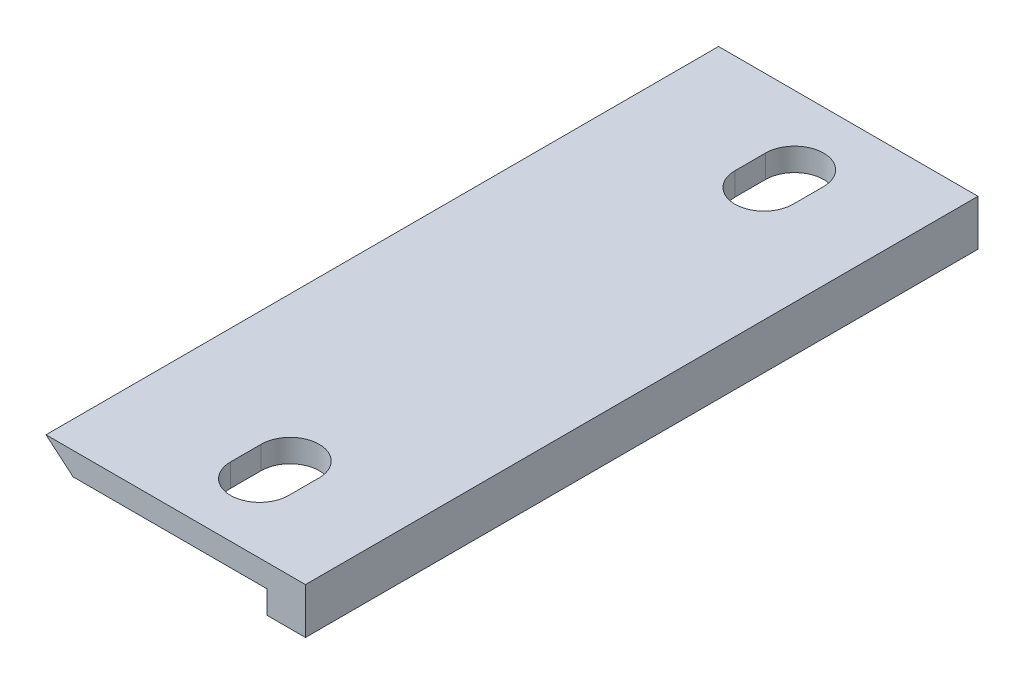
SolidWorks part; units mm, degrees
ref_plane "Спереди" through (0, 0, 0) normal (0, 0, 1) x (1, 0, 0)
ref_plane "Сверху" through (0, 0, 0) normal (0, 1, 0) x (1, 0, 0)
ref_plane "Справа" through (0, 0, 0) normal (1, 0, 0) x (0, 0, -1)
sketch "Эскиз1" plane through (0, 0, 0) normal (0, 0, 1) x (1, 0, 0)
  line L0 (169.7482, 0) -> (0, 0)
  line L1 (17.7482, -15) -> (144.7482, -15)
  line L2 (144.7482, -15) -> (144.7482, -30)
  line L3 (169.7482, -30) -> (144.7482, -30)
  line L9 (169.7482, -30) -> (169.7482, 0)
  line L10 (0, 0) -> (17.7482, -15)
extrude "Бобышка-Вытянуть1" add sketch "Эскиз1" against normal blind 440
sketch "Эскиз4" plane through (0, 0, 0) normal (0, 1, 0) x (1, 0, 0)
  line L0 (75.7482, 65) -> (75.7482, 45)
  line L1 (113.7482, 45) -> (113.7482, 65)
  line L2 (75.7482, 395) -> (75.7482, 375)
  line L3 (113.7482, 375) -> (113.7482, 395)
  arc A0 (75.7482, 45) -> (113.7482, 45) centre (94.7482, 45) ccw
  arc A1 (113.7482, 65) -> (75.7482, 65) centre (94.7482, 65) ccw
  arc A2 (75.7482, 375) -> (113.7482, 375) centre (94.7482, 375) ccw
  arc A3 (113.7482, 395) -> (75.7482, 395) centre (94.7482, 395) ccw
extrude "Вырез-Вытянуть1" cut sketch "Эскиз4" against normal through all
